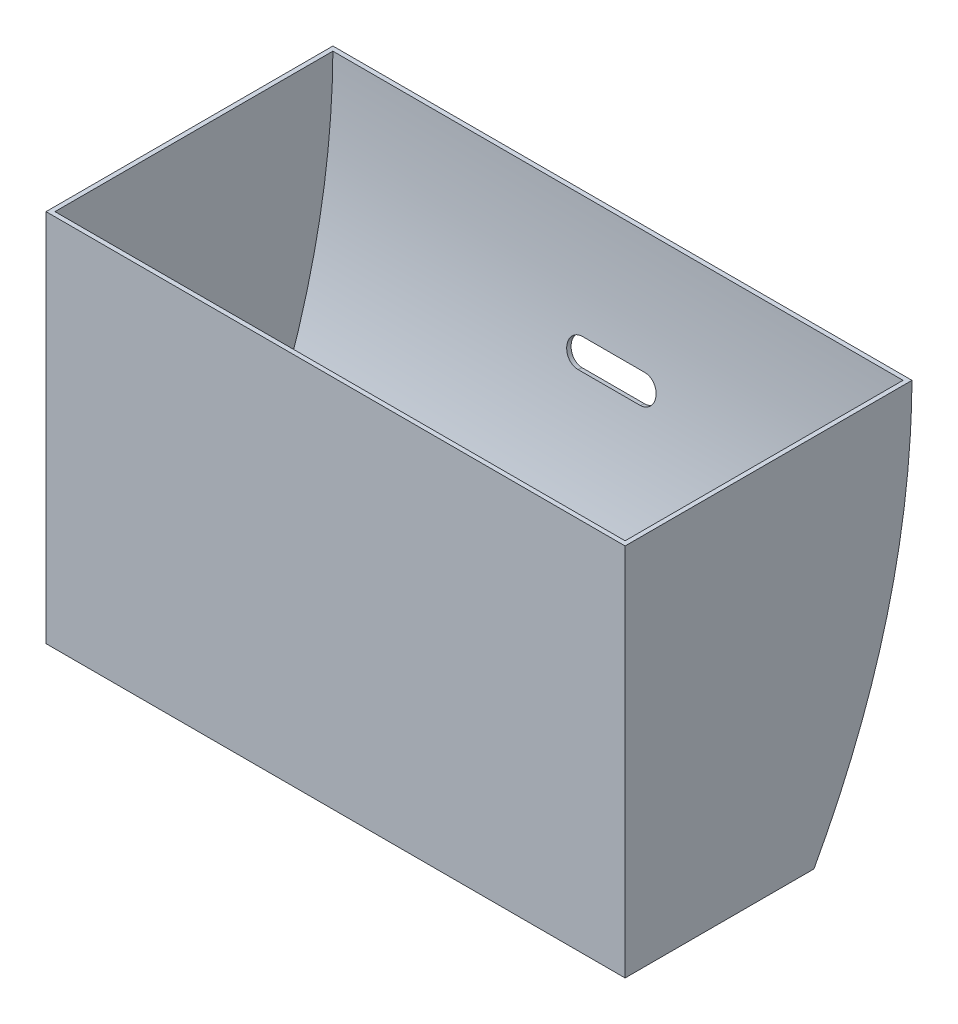
SolidWorks part; units mm, degrees
ref_plane "Front Plane" through (0, 0, 0) normal (0, 0, 1) x (1, 0, 0)
ref_plane "Top Plane" through (0, 0, 0) normal (0, 1, 0) x (1, 0, 0)
ref_plane "Right Plane" through (0, 0, 0) normal (1, 0, 0) x (0, 0, -1)
sketch "Sketch1" plane through (0, 0, 0) normal (0, 1, 0) x (1, 0, 0)
  line L1 (0, 0) -> (65, 0)
  line L2 (0, 0) -> (0, 21.2)
  line L3 (0, 21.2) -> (65, 21.2)
  line L4 (65, 0) -> (65, 21.2)
  dimension "D1" = 21.2
  dimension "D2" = 65
extrude "Boss-Extrude1" add sketch "Sketch1" along normal blind 42
sketch "Sketch2" plane through (65, 0, 0) normal (1, 0, 0) x (0, 0, -1)
  line L0 (21.2, 0) -> (21.2, 29.2)
  line L1 (21.2, 42) -> (21.2, 0) construction
  line L2 (32.2, 42) -> (21.2, 42)
  line L3 (21.2, 42) -> (21.2, 29.2)
  line L4 (0, 42) -> (21.2, 42) construction
  spline S0 degree 2 poles (21.2, 0) (32.0779, 19.8877) (32.2, 42) knots 0 0 0 1 1 1
  dimension "D1" = 29.2
  dimension "D2" = 10
  dimension "D3" = 11
  dimension "D4" = 0
extrude "Boss-Extrude2" add sketch "Sketch2" against normal up to surface (65 mm away) contours S0 L2 L3 L0 up to face at (0, 21, -10.6)
shell "Shell3" thickness 0.5 removed face at (32.5, 42, -16.1)
sketch "Sketch3" plane through (0, 0, 0) normal (0, -1, 0) x (1, 0, 0)
  line L0 (0, 0) -> (65, 0) construction
  line L2 (65, 0) -> (65, -21.2) construction
  circle A0 centre (63, -4.05) radius 0.93
  dimension "D1" = 1.86
  dimension "D2" = 4.05
  dimension "D3" = 2
extrude "Cut-Extrude1" cut sketch "Sketch3" against normal blind 1
pattern_linear "LPattern1" count 13 spacing 5 along (-1, 0, 0) count 5 spacing 3.275 along (0, 0, -1) of "Cut-Extrude1"
sketch "Sketch5" plane through (0, 0, 0) normal (0, -1, 0) x (1, 0, 0)
  circle A0 centre (60.5, -5.6875) radius 0.93
  circle A2 centre (63, -7.325) radius 0.93 construction
  circle A3 centre (63, -4.05) radius 0.93 construction
  dimension "D1" = 1.86
  dimension "D2" = 2.5
  dimension "D3" = 1.6375
extrude "Cut-Extrude2" cut sketch "Sketch5" against normal blind 1
pattern_linear "LPattern2" count 12 spacing 5 along (-1, 0, 0) count 4 spacing 3.275 along (0, 0, -1) of "Cut-Extrude2"
ref_axis "Axis2" through (33, -8.527, -4.05) along (0, 1, 0)
sketch "Sketch6" plane through (0, 0, 0) normal (0, 0, 1) x (1, 0, 0)
  line L0 (29.5, 27.7) -> (36.5, 27.7) construction
  line L1 (29.5, 29.2) -> (36.5, 29.2)
  line L2 (29.5, 26.2) -> (36.5, 26.2)
  line L3 (0, 0) -> (65, 0) construction
  line L5 (33, 0.5) -> (33, 0) construction
  arc A0 (29.5, 29.2) -> (29.5, 26.2) centre (29.5, 27.7) ccw
  arc A1 (36.5, 26.2) -> (36.5, 29.2) centre (36.5, 27.7) ccw
  point P2 (33, 27.7)
  dimension "D2" = 7
  dimension "D3" = 27.7
  dimension "D1" = 3
ref_axis "Axis3" through (33, 27.7, -57.1814) along (0, 0, 1)
ref_point "Point1"
ref_plane "Plane1" through (33, 27.7, -30.957) normal (0, -0.1687, -0.9857) x (-1, 0, 0)
sketch "Sketch7" plane through (5, -3.4198, -25.6321) normal (0, 0.1687, 0.9857) x (1, 0, 0)
  line L0 (24.5, 31.572) -> (31.5, 31.572) construction
  line L1 (24.5, 33.072) -> (31.5, 33.072)
  line L2 (24.5, 30.072) -> (31.5, 30.072)
  arc A0 (24.5, 33.072) -> (24.5, 30.072) centre (24.5, 31.572) ccw
  arc A1 (31.5, 30.072) -> (31.5, 33.072) centre (31.5, 31.572) ccw
  point P2 (28, 31.572)
  dimension "D2" = 7
  dimension "D1" = 3
extrude "Cut-Extrude4" cut sketch "Sketch7" along normal up to next
